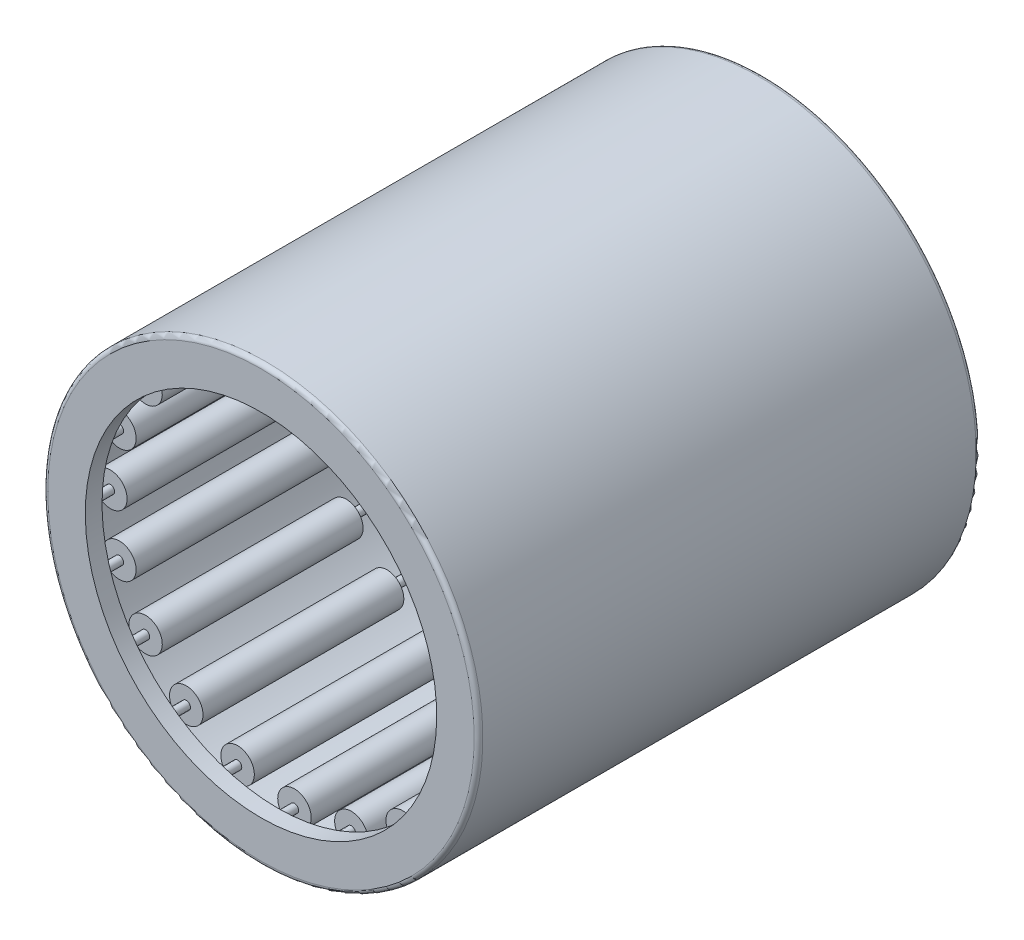
SolidWorks part; units mm, degrees
material "Alloy Steel"
ref_plane "Front Plane" through (0, 0, 0) normal (0, 0, 1) x (1, 0, 0)
ref_plane "Top Plane" through (0, 0, 0) normal (0, 1, 0) x (1, 0, 0)
ref_plane "Right Plane" through (0, 0, 0) normal (1, 0, 0) x (0, 0, -1)
sketch "Sketch1" plane through (0, 0, 0) normal (1, 0, 0) x (0, 0, -1)
  line L0 (-15, 0) -> (15, 0) construction
  line L1 (0, 0) -> (0, 13) construction
  line L2 (-15, 0) -> (-15, 13) construction
  line L3 (-15, 13) -> (15, 13)
  line L4 (15, 13) -> (15, 0) construction
  line L5 (15, 0) -> (14, 0) construction
  line L6 (14, 0) -> (14, 12) construction
  line L7 (14, 12) -> (-14, 12)
  line L8 (-14, 12) -> (-14, 0) construction
  line L9 (-14, 0) -> (-15, 0) construction
  line L10 (-15, 13) -> (-15, 10.5)
  line L11 (-15, 10.5) -> (-14, 10.5)
  line L12 (-14, 10.5) -> (-14, 12)
  line L13 (14, 13) -> (14, 12) construction
  line L14 (14, 12) -> (14, 10.5)
  line L15 (14, 10.5) -> (15, 10.5)
  line L16 (15, 10.5) -> (15, 13)
  line L17 (14, 12) -> (14, 11) construction
  line L18 (14, 11) -> (14, 10) construction
  point P5 (0, 10)
  dimension "Width" = 30
  dimension "OD" = 26
  dimension "Shaft Dia" = 20
revolve "Revolve1" add sketch "Sketch1" angle 360 about L0
sketch "Sketch2" plane through (0, 0, 0) normal (1, 0, 0) x (0, 0, -1)
  line L0 (14, 12) -> (-14, 12) construction
  line L1 (-13, 11) -> (13, 11) construction
  line L2 (-13, 11) -> (-13, 12) construction
  line L3 (-13, 12) -> (-1, 12)
  line L4 (13, 11) -> (13, 12) construction
  line L5 (14, 10.5) -> (15, 10.5) construction
  line L6 (-14, 11) -> (-13, 11) construction
  line L7 (13, 11) -> (14, 11) construction
  line L8 (-15, 10.5) -> (-14, 10.5) construction
  line L9 (-13, 11.25) -> (-13, 10.75) construction
  line L10 (-14, 11) -> (-14, 10.5) construction
  line L11 (-13, 12) -> (-13, 11.25)
  line L12 (13, 12) -> (13, 11.25)
  line L13 (13, 11.25) -> (1, 11.25)
  line L14 (0, 12) -> (0, 10) construction
  line L15 (-14, 10.5) -> (-14, 12) construction
  line L16 (-13, 10.75) -> (-14, 10.75) construction
  line L17 (-15, 0) -> (15, 0) construction
  line L18 (-1, 12) -> (-1, 11.25)
  line L19 (1, 12) -> (1, 11.25)
  line L20 (1, 12) -> (13, 12)
  line L21 (-1, 11.25) -> (-13, 11.25)
  line L22 (-1, 12) -> (0, 12) construction
  line L23 (0, 12) -> (1, 12) construction
  line L31 (15, -13) -> (15, 13) construction
  line L32 (14, 12) -> (14, 10.5) construction
  point P16 (0, 11)
  point P31 (0, 11)
revolve "Revolve2" add sketch "Sketch2" angle 360 about L1
sketch "Sketch3" plane through (0, 0, 0) normal (1, 0, 0) x (0, 0, -1)
  line L0 (14, 12) -> (14, 10.5) construction
  line L1 (-14, 11) -> (14, 11)
  line L2 (-14, 11) -> (-14, 11.25)
  line L3 (-14, 11.25) -> (14, 11.25)
  line L4 (14, 11) -> (14, 11.25)
  line L5 (0, 0) -> (15, 0) construction
  line L6 (15, -13) -> (15, 13) construction
  line L7 (14, -11) -> (14, -11.25) construction
  line L8 (-14, -11.25) -> (14, -11.25) construction
  line L9 (-14, -11) -> (-14, -11.25) construction
  line L10 (-14, -11) -> (14, -11) construction
revolve "Revolve3" add sketch "Sketch3" angle 360 about L1
ref_axis "Axis1" through (0, 0, -15) along (0, 0, 1)
pattern_circular "CirPattern1" count 20 every 18 about axis through (0, 0, -15) along (0, 0, 1) of bodies 166 1001 167
fillet "Fillet1" radius 0.26 2 edges at (0, -13, -15) (0, -13, 15)
sketch "Sketch4" plane through (0, 0, 0) normal (1, 0, 0) x (0, 0, -1)
  line L0 (13, 12) -> (13, 11.25) construction
  line L1 (14.74, 10) -> (13, 10)
  line L2 (14.74, 10) -> (14.74, 10.5)
  line L3 (14.74, 10.5) -> (13, 10.5)
  line L4 (13, 10) -> (13, 10.5)
  line L5 (-15, 10.5) -> (-14, 10.5) construction
  line L6 (14.74, -13) -> (14.74, 13) construction
revolve "Revolve4" [suppressed] add sketch "Sketch4" angle 360 about L0
sketch "Sketch5" plane through (0, 0, 0) normal (1, 0, 0) x (0, 0, -1)
  line L0 (-14.74, 13) -> (-14.74, -13) construction
  line L1 (-13, 10) -> (-14.74, 10)
  line L2 (-13, 10) -> (-13, 10.5)
  line L3 (-13, 10.5) -> (-14.74, 10.5)
  line L4 (-14.74, 10) -> (-14.74, 10.5)
  line L5 (-13, 12) -> (-13, 11.25) construction
revolve "Revolve5" [suppressed] add sketch "Sketch5" angle 360 about L0
sketch "Front View" plane through (0, 0, 0) normal (0, 0, 1) x (1, 0, 0)
  circle A0 centre (0, 0) radius 10 construction
  circle A1 centre (0, 0) radius 13 construction
  dimension "OD" = 26
  dimension "ID" = 20
sketch "Right View" plane through (0, 0, 0) normal (1, 0, 0) x (0, 0, -1)
  line L0 (-15, 13) -> (15, 13) construction
  point P4 (0, 13)
  dimension "Width" = 30
ref_axis "Center Axis 1" through (0, 0, -14.74) along (0, 0, 1)
ref_plane "Contact Plane 1" through (0, 0, 15) normal (0, 0, 1) x (1, 0, 0)
ref_plane "Contact Plane 2" through (0, 0, -15) normal (0, 0, -1) x (-1, 0, 0)
equation "\"Rollers@CirPattern1\" = \"OD@Sketch1\"*.75"
equation "\"D1@Fillet1\" = \"OD@Sketch1\"*.01"
equation "\"Angle@CirPattern1\"= 360 / \"Rollers@CirPattern1\""
equation "\"ID@Front View\" = \"Shaft Dia@Sketch1\""
equation "\"OD@Front View\" = \"OD@Sketch1\""
equation "\"Width@Right View\" = \"Width@Sketch1\""
